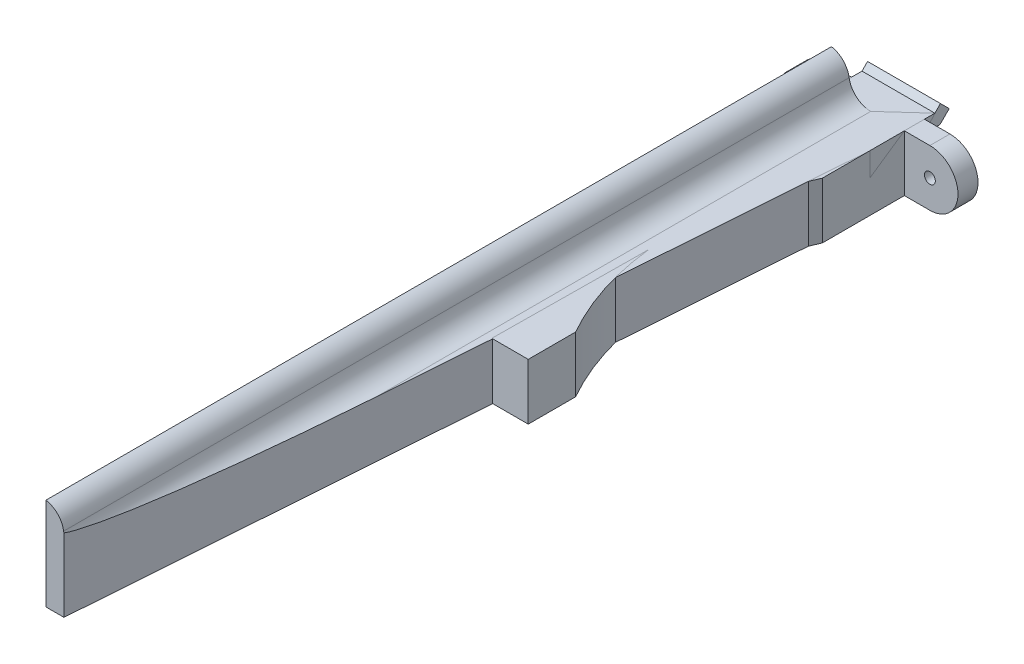
SolidWorks part; units mm, degrees
ref_plane "Front Plane" through (0, 0, 0) normal (0, 0, 1) x (1, 0, 0)
ref_plane "Top Plane" through (0, 0, 0) normal (0, 1, 0) x (1, 0, 0)
ref_plane "Right Plane" through (0, 0, 0) normal (1, 0, 0) x (0, 0, -1)
sketch "Sketch2" plane through (0, 0, 0) normal (0, 0, 1) x (1, 0, 0)
  line L0 (0, 5.9203) -> (0, 8.9503) construction
  line L1 (-5, -5.8182) -> (5, -5.8182)
  line L2 (-5, -5.8182) -> (-5, 8.9503)
  line L3 (-5, 8.9503) -> (5, 8.9503)
  line L4 (5, -5.8182) -> (5, 8.9503)
  line L7 (13.4766, 5.9203) -> (-18.5234, 5.9203) construction
  line L8 (0, -5.8182) -> (0, -2.7882) construction
  point P0 (0, 0)
  dimension "D1" = 10
extrude "Boss-Extrude1" add sketch "Sketch2" along normal blind 5
sketch "Sketch8" plane through (-5, 0, 0) normal (-1, 0, 0) x (0, 0, 1)
  line L6 (-0.15, 5.7703) -> (0, 5.7703)
  line L7 (0, 8.9503) -> (0, -5.8182) construction
  line L8 (0, 5.7703) -> (0, 4.0703)
  line L9 (0, 4.0703) -> (-0.15, 4.0703)
  line L11 (-0.15, -1.9297) -> (0, -1.9297)
  line L12 (-2.1379, 4.0703) -> (-0.15, 4.0703)
  line L13 (-0.15, 4.0703) -> (-0.15, 5.7703)
  line L14 (-0.15, 5.7703) -> (-1.4337, 5.7703)
  line L15 (-1.4337, 5.7703) -> (-2.2, 6.5366)
  line L16 (-2.2, 6.5366) -> (-3.4021, 5.3345)
  line L17 (-3.4021, 5.3345) -> (-2.1379, 4.0703)
  line L18 (-2.1379, 4.0703) -> (-0.15, 4.0703)
  line L20 (-0.15, 5.7703) -> (-1.4337, 5.7703)
  line L21 (-1.4337, 5.7703) -> (-2.2, 6.5366)
  line L22 (-2.2, 6.5366) -> (-3.4021, 5.3345)
  line L23 (-3.4021, 5.3345) -> (-2.1379, 4.0703)
  line L24 (-2.1379, -1.9297) -> (-0.15, -1.9297)
  line L25 (-0.15, -1.9297) -> (-0.15, -0.2297)
  line L26 (-0.15, -0.2297) -> (-1.4337, -0.2297)
  line L27 (-1.4337, -0.2297) -> (-2.2, 0.5366)
  line L28 (-2.2, 0.5366) -> (-3.4021, -0.6655)
  line L29 (-3.4021, -0.6655) -> (-2.1379, -1.9297)
  line L30 (-2.1379, -1.9297) -> (-0.15, -1.9297)
  line L32 (-0.15, -0.2297) -> (-1.4337, -0.2297)
  line L33 (-1.4337, -0.2297) -> (-2.2, 0.5366)
  line L34 (-2.2, 0.5366) -> (-3.4021, -0.6655)
  line L35 (-3.4021, -0.6655) -> (-2.1379, -1.9297)
  line L37 (-0.15, -0.2297) -> (0, -0.2297)
  line L38 (0, -1.9297) -> (0, -0.2297)
  dimension "D1" = 0.15
  dimension "D2" = 0.15
extrude "Boss-Extrude4" add sketch "Sketch8" against normal up to surface (10 mm away) up to face at (5, 1.566, 2.5)
sketch "Sketch9" plane through (0, 0, 0) normal (0, 0, -1) x (-1, 0, 0)
  line L4 (-5, 8.9503) -> (-5, 5.7703)
  line L5 (-5, 5.7703) -> (5, 5.7703)
  line L6 (5, 5.7703) -> (5, 8.9503)
  line L7 (5, 8.9503) -> (-5, 8.9503)
  line L8 (-5, 8.9503) -> (-5, 5.7703)
  line L10 (5, 5.7703) -> (5, 8.9503)
  line L11 (5, 8.9503) -> (-5, 8.9503)
  line L16 (5, -1.9297) -> (-5, -1.9297)
  line L17 (-5, -1.9297) -> (-5, -5.8182)
  line L18 (-5, -5.8182) -> (5, -5.8182)
  line L19 (5, -5.8182) -> (5, -1.9297)
  line L21 (-5, -1.9297) -> (-5, -5.8182)
  line L22 (-5, -5.8182) -> (5, -5.8182)
  line L23 (5, -5.8182) -> (5, -1.9297)
  line L26 (-5, 5.7703) -> (5, 5.7703)
  line L27 (5, -1.9297) -> (-5, -1.9297)
  dimension "D1" = 0
  dimension "D2" = 0
extrude "Cut-Extrude3" cut sketch "Sketch9" against normal blind 5
sketch "Sketch10" plane through (0, 5.7703, 0) normal (0, 1, 0) x (1, 0, 0)
  line L0 (-5, -5) -> (-5, -10.5)
  line L1 (-5, -10.5) -> (1.3524, -55.7)
  line L2 (1.3524, -55.7) -> (6.3524, -55.7)
  line L3 (-5, -5) -> (5, -5)
  line L4 (-120.9789, 453.7107) -> (412.3545, 453.7107) construction
  line L5 (6.3524, -55.7) -> (6.3524, -49.2)
  line L6 (5, -5) -> (5, -14)
  arc A1 (5, -14) -> (6.3524, -49.2) centre (39.6089, -30.2962) ccw
  dimension "D1" = 172
  dimension "D2" = 45.2
  dimension "D3" = 5
  dimension "D4" = 6.5
  dimension "D5" = 5.5
  dimension "D6" = 9
extrude "Boss-Extrude5" add sketch "Sketch10" against normal up to surface (7.7 mm away) up to face at (0, -1.9297, 1.4311)
ref_plane "Plane1" through (0, 0, 2.75) normal (0, 0, 1) x (1, 0, 0)
sketch "Sketch12" plane through (0, 0, 0) normal (0, 0, 1) x (1, 0, 0)
  line L0 (5, 5.7703) -> (8.5, 5.7703)
  line L1 (8.5, -1.9297) -> (5, -1.9297)
  line L2 (5, -1.9297) -> (5, 5.7703)
  line L3 (1.3524, 5.7703) -> (6.3524, 5.7703) construction
  line L4 (1.3524, -1.9297) -> (6.3524, -1.9297) construction
  line L5 (5, 5.3345) -> (5, 6.5366) construction
  line L6 (6.3524, 5.7703) -> (1.3552, 5.7703) construction
  arc A0 (8.5, 5.7703) -> (8.5, -1.9297) centre (8.5, 1.9203) cw
  circle A1 centre (8.5, 1.9203) radius 0.75
  dimension "D1" = 1.5
  dimension "D2" = 3.5
extrude "Boss-Extrude7" add sketch "Sketch12" along normal up to surface (2.75 mm away) up to plane "Plane1"
mirror "Mirror1" about plane through (0, 0, 0) normal (1, 0, 0) of bodies 112
fillet "Fillet1" radius 2.5 4 edges at (-5, 1.9203, 14) (-6.3524, 1.9203, 49.2) (-1.3524, 1.9203, 55.7) (-6.3524, 1.9203, 55.7)
sketch "Sketch13" plane through (0, 5.7703, 0) normal (0, 1, 0) x (1, 0, 0)
  line L1 (5, -10.5) -> (-8.6739, -10.5)
  line L2 (5, -10.5) -> (5, -58.128)
  line L3 (5, -58.128) -> (-8.6739, -58.128)
  line L4 (-8.6739, -10.5) -> (-8.6739, -58.128)
extrude "Cut-Extrude4" cut sketch "Sketch13" against normal blind 100
sketch "Sketch14" plane through (0, 0, 10.5) normal (0, 0, 1) x (1, 0, 0)
  line L1 (-5, 5.7703) -> (5, 5.7703)
  line L2 (-5, 5.7703) -> (-5, -1.9297)
  line L3 (-5, -1.9297) -> (5, -1.9297)
  line L4 (5, 5.7703) -> (5, -1.9297)
extrude "Boss-Extrude8" add sketch "Sketch14" along normal blind 100
sketch "Sketch15" plane through (0, 5.7703, 0) normal (0, 1, 0) x (1, 0, 0)
  line L0 (5, -7.4894) -> (-2.5387, -110.5)
  line L1 (5, -110.5) -> (5, 1.4337) construction
  line L2 (5, -110.5) -> (-5, -110.5) construction
  line L3 (-2.5387, -110.5) -> (5, -110.5)
  line L4 (5, -110.5) -> (5, -7.4894)
extrude "Cut-Extrude5" cut sketch "Sketch15" against normal blind 100
sketch "Sketch16" plane through (0, 5.7703, 0) normal (0, 1, 0) x (1, 0, 0)
  line L1 (-5, -2.75) -> (-2.5387, -2.75)
  line L2 (-5, -2.75) -> (-5, -110.5)
  line L3 (-5, -110.5) -> (-2.5387, -110.5)
  line L4 (-2.5387, -2.75) -> (-2.5387, -110.5)
extrude "Boss-Extrude9" add sketch "Sketch16" along normal blind 5
fillet "Fillet3" radius 3 1 edges at (-2.5387, 10.7703, 56.625)
fillet "Fillet4" radius 3 1 edges at (-2.5387, 5.7703, 56.625)
